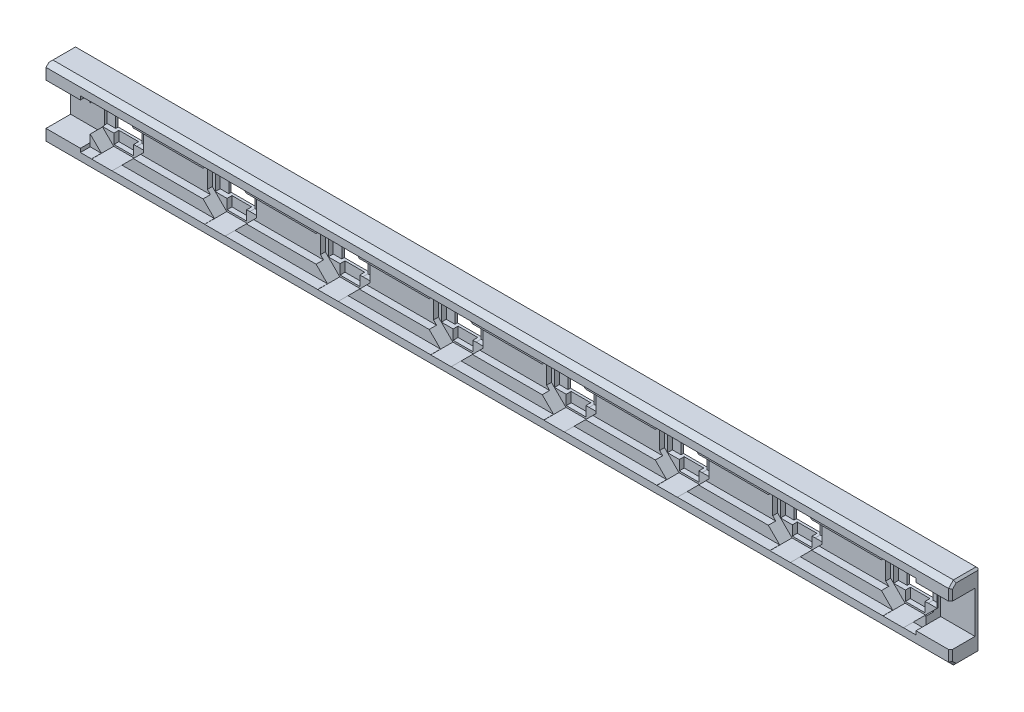
SolidWorks part; units mm, degrees
ref_plane "Front Plane" through (0, 0, 0) normal (0, 0, 1) x (1, 0, 0)
ref_plane "Top Plane" through (0, 0, 0) normal (0, 1, 0) x (1, 0, 0)
ref_plane "Right Plane" through (0, 0, 0) normal (1, 0, 0) x (0, 0, -1)
sketch "Sketch1" plane through (0, 0, 0) normal (0, 0, 1) x (1, 0, 0)
  line L1 (-137.75, 25.6543) -> (46.25, 25.6543)
  line L2 (-137.75, 25.6543) -> (-137.75, 10.6543)
  line L3 (-137.75, 10.6543) -> (46.25, 10.6543)
  line L4 (46.25, 25.6543) -> (46.25, 10.6543)
  dimension "D1" = 184
  dimension "D2" = 15
extrude "Boss-Extrude1" add sketch "Sketch1" along normal blind 6
sketch "Sketch12" plane through (46.25, 0, 0) normal (1, 0, 0) x (0, 0, -1)
  line L0 (-6, 25.6543) -> (-6, 24.6543)
  line L1 (-6, 10.6543) -> (-6, 25.6543) construction
  line L2 (-6, 24.6543) -> (-5, 25.6543)
  line L3 (-6, 25.6543) -> (0, 25.6543) construction
  line L4 (-5, 25.6543) -> (-6, 25.6543)
  line L5 (-6, 10.6543) -> (-5, 10.6543)
  line L6 (-6, 10.6543) -> (0, 10.6543) construction
  line L7 (-5, 10.6543) -> (-6, 11.6543)
  line L8 (-6, 10.6543) -> (-6, 25.6543) construction
  line L9 (-6, 11.6543) -> (-6, 10.6543)
  dimension "D1" = 1
  dimension "D2" = 1
  dimension "D3" = 1
extrude "Cut-Extrude8" cut sketch "Sketch12" against normal up to surface (184 mm away) up to face at (-137.75, 18.1543, 3)
sketch "Sketch13" plane through (0, 0, 0) normal (0, 0, -1) x (-1, 0, 0)
  line L0 (137.75, 25.6543) -> (137.75, 10.6543) construction
  line L1 (135.25, 23.1543) -> (135.75, 23.1543)
  line L2 (135.25, 23.1543) -> (135.25, 13.1543)
  line L3 (135.25, 13.1543) -> (135.75, 13.1543)
  line L4 (135.75, 23.1543) -> (135.75, 13.1543)
  line L5 (-46.25, 25.6543) -> (137.75, 25.6543) construction
  dimension "D1" = 2
  dimension "D2" = 0.5
  dimension "D3" = 10
  dimension "D4" = 2.5
extrude "Cut-Extrude9" cut sketch "Sketch13" against normal blind 0.6
fillet "Fillet1" radius 0.25 1 edges at (-135.75, 18.1543, 0)
fillet "Fillet2" radius 0.25 4 edges at (-135.5, 23.1543, 0.6) (-135.75, 18.1543, 0.6) (-135.5, 13.1543, 0.6) (-135.25, 18.1543, 0.6)
chamfer "Chamfer1" distance 0.4 angle 45 2 edges at (-45.75, 10.6543, 0) (-45.75, 25.6543, 0)
chamfer "Chamfer2" distance 0.4 angle 45 2 edges at (46.25, 18.1543, 0) (-137.75, 18.1543, 0)
chamfer "Chamfer3" distance 0.4 angle 45 2 edges at (-137.75, 10.6543, 2.7) (-137.75, 25.6543, 2.7)
chamfer "Chamfer5" distance 0.4 angle 45 5 edges at (46.25, 25.1543, 5.5) (46.25, 25.6543, 2.7) (46.25, 18.1543, 6) (46.25, 11.1543, 5.5) (46.25, 10.6543, 2.7)
sketch "Sketch15" plane through (0, 0, 6) normal (0, 0, 1) x (1, 0, 0)
  line L0 (-137.75, 24.6543) -> (-137.75, 11.6543) construction
  line L1 (-121.3821, 20.2328) -> (-124.3215, 23.1722)
  line L2 (-124.3215, 23.1722) -> (-128.4785, 23.1722)
  line L3 (-128.4785, 23.1722) -> (-131.4179, 20.2328)
  line L4 (-131.4179, 20.2328) -> (-131.4179, 16.0758)
  line L5 (-131.4179, 16.0758) -> (-128.4785, 13.1364)
  line L6 (-128.4785, 13.1364) -> (-124.3215, 13.1364)
  line L7 (-124.3215, 13.1364) -> (-121.3821, 16.0758)
  line L8 (-121.3821, 16.0758) -> (-121.3821, 20.2328)
  line L9 (-137.35, 25.6543) -> (45.85, 25.6543) construction
  line L10 (-137.75, 11.6543) -> (45.85, 11.6543) construction
  circle A0 centre (-126.4, 18.1543) radius 5.0179 construction
  dimension "D1" = 11.35
  dimension "D2" = 7.5
extrude "Cut-Extrude10" cut sketch "Sketch15" against normal blind 4.5
sketch "Sketch16" plane through (0, 0, 1.5) normal (0, 0, 1) x (1, 0, 0)
  line L1 (-129.0679, 20.7864) -> (-123.7679, 20.7864)
  line L2 (-129.0679, 20.7864) -> (-129.0679, 15.4864)
  line L3 (-129.0679, 15.4864) -> (-123.7679, 15.4864)
  line L4 (-123.7679, 20.7864) -> (-123.7679, 15.4864)
  line L5 (-131.4179, 20.2328) -> (-131.4179, 16.0758) construction
  line L6 (-128.4785, 13.1364) -> (-124.3215, 13.1364) construction
  point P4 (-129.0679, 18.1364)
  point P7 (-131.4179, 18.1543)
  point P10 (-126.4, 13.1364)
  point P11 (-126.4179, 15.4864)
  dimension "D1" = 5.3
  dimension "D2" = 5.3
  dimension "D3" = 2.35
  dimension "D4" = 2.35
extrude "Cut-Extrude11" cut sketch "Sketch16" against normal blind 4.5
sketch "Sketch17" plane through (0, 0, 1.5) normal (0, 0, 1) x (1, 0, 0)
  line L0 (-129.0679, 15.4864) -> (-123.7679, 15.4864) construction
  line L1 (-128.4179, 15.4864) -> (-124.4179, 15.4864)
  line L2 (-128.4179, 15.4864) -> (-128.4179, 13.4864)
  line L3 (-128.4179, 13.4864) -> (-124.4179, 13.4864)
  line L4 (-124.4179, 15.4864) -> (-124.4179, 13.4864)
  line L5 (-123.7679, 20.7864) -> (-129.0679, 20.7864) construction
  line L6 (-128.4179, 20.7864) -> (-124.4179, 20.7864)
  line L7 (-128.4179, 20.7864) -> (-128.4179, 22.7864)
  line L8 (-128.4179, 22.7864) -> (-124.4179, 22.7864)
  line L9 (-124.4179, 20.7864) -> (-124.4179, 22.7864)
  line L10 (-123.7679, 15.4864) -> (-123.7679, 20.7864) construction
  dimension "D1" = 4
  dimension "D2" = 4
  dimension "D3" = 2
  dimension "D4" = 2
  dimension "D5" = 0.65
  dimension "D6" = 0.65
extrude "Cut-Extrude12" cut sketch "Sketch17" against normal blind 1
sketch "Sketch18" plane through (0, 0, 1.5) normal (0, 0, 1) x (1, 0, 0)
  line L1 (-129.0679, 15.4864) -> (-130.8179, 15.4864)
  line L2 (-129.0679, 15.4864) -> (-129.0679, 20.8045)
  line L3 (-129.0679, 20.8045) -> (-130.8179, 20.8045)
  line L4 (-130.8179, 15.4864) -> (-130.8179, 20.8045)
  line L5 (-123.7679, 20.7864) -> (-122.0179, 20.7864)
  line L6 (-123.7679, 20.7864) -> (-123.7679, 15.5045)
  line L7 (-123.7679, 15.5045) -> (-122.0179, 15.5045)
  line L8 (-122.0179, 20.7864) -> (-122.0179, 15.5045)
  dimension "D1" = 1.75
  dimension "D2" = 1.75
extrude "Cut-Extrude13" cut sketch "Sketch18" against normal blind 1
pattern_linear "LPattern1" count 8 spacing 23 along (1, 0, 0) of "Cut-Extrude10", "Cut-Extrude11", "Cut-Extrude12", "Cut-Extrude13"
sketch "Sketch19" plane through (0, 0, 6) normal (0, 0, 1) x (1, 0, 0)
  line L0 (-137.75, 24.6543) -> (-137.75, 11.6543) construction
  line L1 (-137.75, 22.4043) -> (-130.75, 22.4043)
  line L2 (-137.75, 22.4043) -> (-137.75, 13.9043)
  line L3 (-137.75, 13.9043) -> (-130.75, 13.9043)
  line L4 (-130.75, 22.4043) -> (-130.75, 13.9043)
  line L6 (-137.35, 10.6543) -> (45.85, 10.6543) construction
  line L14 (46.25, 24.4886) -> (46.25, 11.82) construction
  line L15 (46.25, 22.4043) -> (39.25, 22.4043)
  line L16 (46.25, 22.4043) -> (46.25, 13.9043)
  line L17 (46.25, 13.9043) -> (39.25, 13.9043)
  line L18 (39.25, 22.4043) -> (39.25, 13.9043)
  dimension "D1" = 8.5
  dimension "D2" = 3.25
  dimension "D3" = 7
  dimension "D4" = 8.5
  dimension "D5" = 7
  dimension "D6" = 3.25
extrude "Cut-Extrude14" cut sketch "Sketch19" against normal blind 5
sketch "Sketch20" plane through (0, 0, 6) normal (0, 0, 1) x (1, 0, 0)
  line L0 (-137.35, 10.6543) -> (45.85, 10.6543) construction
  line L1 (39.25, 13.1543) -> (-130.75, 13.1543)
  line L2 (39.25, 13.1543) -> (39.25, 23.1543)
  line L3 (39.25, 23.1543) -> (-130.75, 23.1543)
  line L4 (-130.75, 13.1543) -> (-130.75, 23.1543)
  line L6 (-130.75, 20.9007) -> (-130.75, 22.4043) construction
  dimension "D1" = 10
  dimension "D2" = 2.5
  dimension "D3" = 0
extrude "Cut-Extrude15" cut sketch "Sketch20" against normal blind 2
sketch "Sketch21" plane through (-62.4179, 0, 0) normal (1, 0, 0) x (0, 0, -1)
  line L0 (-4, 20.6007) -> (-4, 22.4043) construction
  line L3 (-4, 20.8507) -> (-2.5, 20.8507)
  line L4 (-4, 20.8507) -> (-4, 15.4579)
  line L5 (-4, 15.4579) -> (-2.5, 15.4579)
  line L6 (-2.5, 20.8507) -> (-2.5, 15.4579)
  line L7 (-1.5, 20.6007) -> (-4, 20.6007) construction
  line L8 (-4, 15.7079) -> (-1.5, 15.7079) construction
  dimension "D8" = 0.25
  dimension "D9" = 0.25
  dimension "D10" = 1.5
extrude "Cut-Extrude16" cut sketch "Sketch21" against normal through all both and the other way through all
